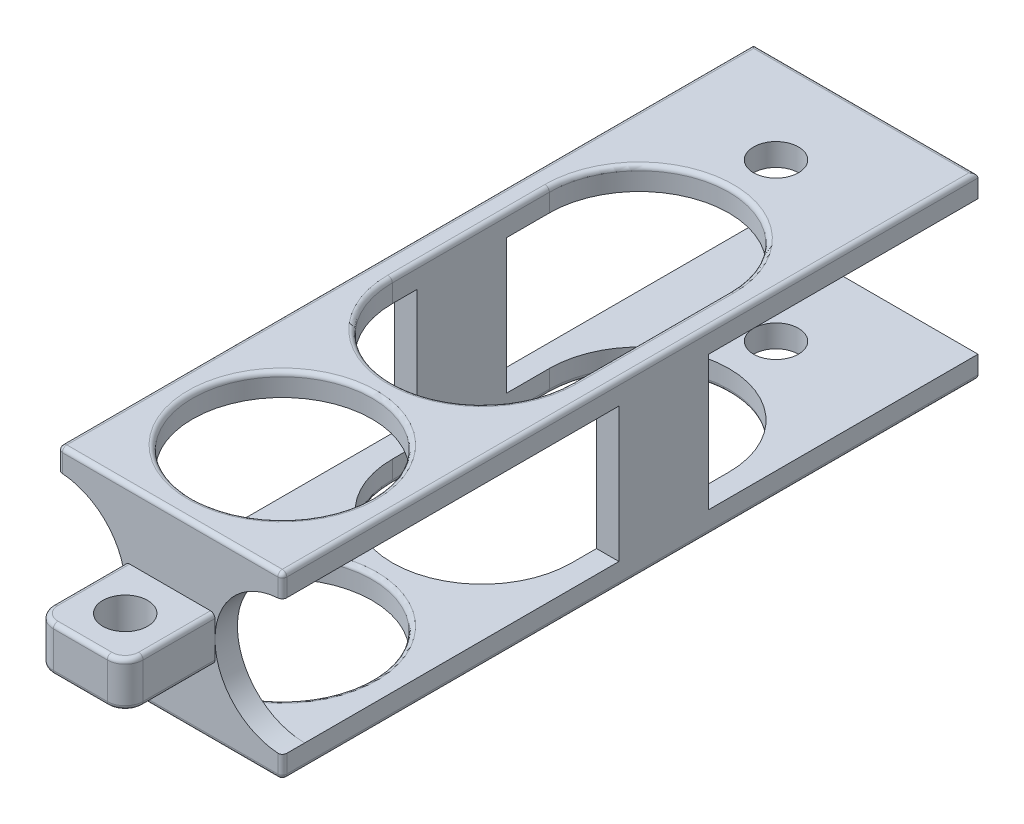
SolidWorks part; units mm, degrees
ref_plane "Front Plane" through (0, 0, 0) normal (0, 0, 1) x (1, 0, 0)
ref_plane "Top Plane" through (0, 0, 0) normal (0, 1, 0) x (1, 0, 0)
ref_plane "Right Plane" through (0, 0, 0) normal (1, 0, 0) x (0, 0, -1)
sketch "Sketch1" plane through (0, 0, 0) normal (0, 0, 1) x (1, 0, 0)
  line L1 (12.5, -10) -> (-12.5, -10)
  line L2 (12.5, -10) -> (12.5, 10)
  line L3 (12.5, 10) -> (-12.5, 10)
  line L4 (-12.5, -10) -> (-12.5, 10)
  line L5 (12.5, -10) -> (-12.5, 10) construction
  line L6 (12.5, 10) -> (-12.5, -10) construction
  point P0 (0, 0)
  dimension "D1" = 25
  dimension "D2" = 20
extrude "Boss-Extrude1" add sketch "Sketch1" along normal blind 2.5
sketch "Sketch2" plane through (0, 0, 0) normal (0, 0, -1) x (-1, 0, 0)
  line L0 (12.5, 10) -> (12.5, -10) construction
  line L1 (-12.5, 10) -> (12.5, 10)
  line L2 (-12.5, 10) -> (-12.5, 7.5)
  line L3 (-12.5, 7.5) -> (12.5, 7.5)
  line L4 (12.5, 10) -> (12.5, 7.5)
  line L6 (-12.5, -10) -> (12.5, -10)
  line L7 (-12.5, -10) -> (-12.5, -7.5)
  line L8 (-12.5, -7.5) -> (12.5, -7.5)
  line L9 (12.5, -10) -> (12.5, -7.5)
  dimension "D1" = 2.5
  dimension "D2" = 2.5
extrude "Boss-Extrude2" add sketch "Sketch2" along normal blind 75
sketch "Sketch3" plane through (0, 0, 2.5) normal (0, 0, 1) x (1, 0, 0)
  line L0 (-12.5, 10) -> (-12.5, -10) construction
  line L2 (12.5, -10) -> (12.5, 10) construction
  circle A0 centre (-12.5, 0) radius 7.5
  circle A1 centre (12.5, 0) radius 7.5
  dimension "D1" = 15
  dimension "D2" = 15
extrude "Cut-Extrude1" cut sketch "Sketch3" against normal blind 2.5
sketch "Sketch4" plane through (0, 10, 0) normal (0, 1, 0) x (1, 0, 0)
  circle A0 centre (0, 10) radius 10
  dimension "D1" = 20
  dimension "D2" = 10
extrude "Cut-Extrude2" cut sketch "Sketch4" against normal through all
sketch "Sketch5" plane through (0, 10, 0) normal (0, 1, 0) x (1, 0, 0)
  circle A0 centre (0, 65) radius 2.5
  dimension "D1" = 5
  dimension "D2" = 65
extrude "Cut-Extrude3" cut sketch "Sketch5" against normal through all
sketch "Sketch7" plane through (0, 10, 0) normal (0, 1, 0) x (1, 0, 0)
  line L0 (12.5, -2.5) -> (-12.5, -2.5) construction
  line L1 (-5, -2.5) -> (5, -2.5)
  line L2 (-5, -2.5) -> (-5, -12.5)
  line L3 (-5, -12.5) -> (5, -12.5)
  line L4 (5, -2.5) -> (5, -12.5)
  point P6 (0, -2.5)
  dimension "D1" = 10
  dimension "D2" = 10
extrude "Boss-Extrude3" add sketch "Sketch7" against normal mid plane 5 from offset 10 offset against normal yes
sketch "Sketch8" plane through (0, 2.5, 0) normal (0, 1, 0) x (1, 0, 0)
  line L1 (-5, -12.5) -> (5, -12.5) construction
  circle A0 centre (0, -7.5) radius 2.5
  dimension "D1" = 5
  dimension "D2" = 5
extrude "Cut-Extrude4" cut sketch "Sketch8" against normal through all
fillet "Fillet1" radius 2 2 edges at (-5, 0, 12.5) (5, 0, 12.5)
sketch "Sketch9" plane through (0, 10, 0) normal (0, 1, 0) x (1, 0, 0)
  line L0 (0, 49.75) -> (0, 32.25) construction
  line L1 (10, 49.75) -> (10, 32.25)
  line L2 (-10, 49.75) -> (-10, 32.25)
  arc A0 (10, 49.75) -> (-10, 49.75) centre (0, 49.75) ccw
  arc A1 (-10, 32.25) -> (10, 32.25) centre (0, 32.25) ccw
  point P3 (0, 41)
  dimension "D1" = 10
  dimension "D2" = 17.5
  dimension "D3" = 41
extrude "Cut-Extrude5" cut sketch "Sketch9" against normal through all
sketch "Sketch10" plane through (0, 7.5, 0) normal (0, -1, 0) x (1, 0, 0)
  line L0 (12.5, 2.5) -> (12.5, -75) construction
  line L1 (12.5, -35) -> (10, -35)
  line L2 (12.5, -35) -> (12.5, -45)
  line L3 (12.5, -45) -> (10, -45)
  line L4 (10, -35) -> (10, -45)
  line L5 (10, -32.25) -> (10, -49.75) construction
  line L6 (-12.5, 2.5) -> (-12.5, -75) construction
  line L7 (-12.5, -35) -> (-10, -35)
  line L8 (-12.5, -35) -> (-12.5, -45)
  line L9 (-12.5, -45) -> (-10, -45)
  line L10 (-10, -35) -> (-10, -45)
  line L11 (-10, -49.75) -> (-10, -32.25) construction
  point P16 (-11.25, -45)
  dimension "D1" = 10
  dimension "D2" = 10
  dimension "D3" = 45
extrude "Boss-Extrude4" add sketch "Sketch10" along normal up to next
fillet "Fillet3" radius 0.5 9 edges at (-10, -10, -41) (0, -10, -59.75) (10, -10, -41) (0, -10, -75) (-12.5, -10, -36.25) (0, -10, 2.5) (0, -10, -22.25) (12.5, -10, -36.25) (10, -7.5, -10)
fillet "Fillet4" radius 0.5 8 edges at (10, 10, -41) (0, 10, -22.25) (-10, 10, -41) (0, 10, -75) (-12.5, 10, -36.25) (-10, 10, -10) (0, 10, -59.75) (12.5, 10, -36.25)
fillet "Fillet5" radius 0.5 19 edges at (-12.3536, -9.8536, 2.3536) (12.3536, -9.8536, 2.3536) (5, -2.5, 6.5) (-5, -2.5, 6.5) (-4.4142, -2.5, 11.9142) (0, -2.5, 12.5) (-5, 2.5, 6.5) (-4.4142, 2.5, 11.9142) (0, 2.5, 12.5) (4.4142, 2.5, 11.9142) (12.5, 8.5, 2.5) (12.3536, 9.8536, 2.5) (-12.5, 8.5, 2.5) (-12.3536, 9.8536, 2.5) (-12.5, -8.5, 2.5) (12.5, -8.5, 2.5) (4.4142, -2.5, 11.9142) (5, 2.5, 6.5) (0, 10, 2.5)
